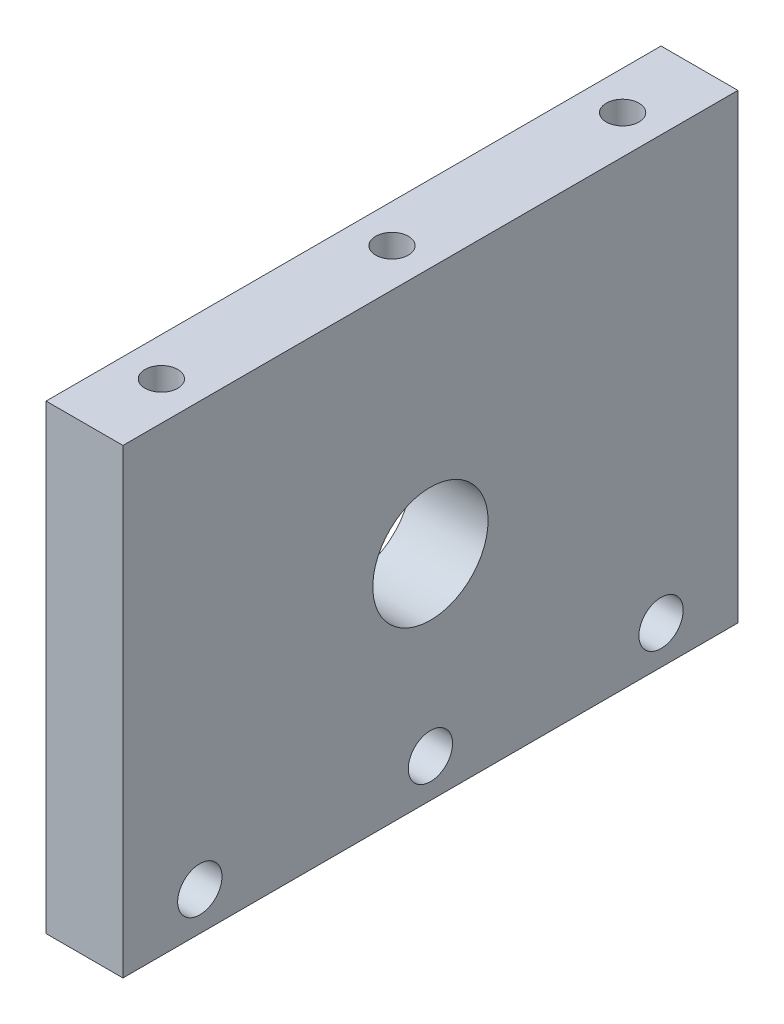
SolidWorks part; units mm, degrees
ref_plane "Front Plane" through (0, 0, 0) normal (0, 0, 1) x (1, 0, 0)
ref_plane "Top Plane" through (0, 0, 0) normal (0, 1, 0) x (1, 0, 0)
ref_plane "Right Plane" through (0, 0, 0) normal (1, 0, 0) x (0, 0, -1)
sketch "Sketch1" plane through (0, 0, 0) normal (1, 0, 0) x (0, 0, -1)
  line L1 (0, 0) -> (-50.8, 0)
  line L2 (0, 0) -> (0, 38.1)
  line L3 (0, 38.1) -> (-50.8, 38.1)
  line L4 (-50.8, 0) -> (-50.8, 38.1)
  dimension "D1" = 38.1
  dimension "D2" = 50.8
extrude "Boss-Extrude1" add sketch "Sketch1" along normal blind 6.35
sketch "Sketch2" plane through (0, 38.1, 0) normal (0, 1, 0) x (1, 0, 0)
  line L0 (0, 0) -> (0, -50.8) construction
  line L1 (6.35, -50.8) -> (0, -50.8) construction
  circle A0 centre (3.175, -44.45) radius 1.7526
  circle A1 centre (3.175, -6.35) radius 1.7526
  circle A3 centre (3.175, -25.4) radius 1.7526
  dimension "D1" = 3.5052
  dimension "D3" = 3.5052
  dimension "D5" = 3.5052
  dimension "D2" = 3.175
  dimension "D4" = 6.35
  dimension "D6" = 25.4
  dimension "D7" = 44.45
sketch "Sketch3" plane through (6.35, 0, 0) normal (1, 0, 0) x (0, 0, -1)
  line L0 (-50.8, 38.1) -> (-50.8, 0) construction
  line L1 (-50.8, 0) -> (0, 0) construction
  circle A0 centre (-44.45, 3.175) radius 1.8288
  circle A1 centre (-25.4, 3.175) radius 1.8288
  circle A2 centre (-6.35, 3.175) radius 1.8288
  dimension "D7" = 3.6576
  dimension "D8" = 3.6576
  dimension "D9" = 3.6576
  dimension "D1" = 6.35
  dimension "D2" = 25.4
  dimension "D3" = 44.45
  dimension "D4" = 3.175
  dimension "D5" = 3.175
  dimension "D6" = 3.175
extrude "Cut-Extrude1" cut sketch "Sketch3" against normal blind 6.35
hole_wizard "#6-32 Tapped Hole1" positions "Sketch10" profile "Sketch11" tap size "#6-32" standard "ANSI Inch"
sketch "Sketch10" plane through (0, 38.1, 0) normal (0, 1, 0) x (1, 0, 0)
  point P0 (3.175, -6.35)
  point P3 (3.175, -25.4)
  point P6 (3.175, -44.45)
sketch "Sketch11" plane through (3.175, 38.1, 6.35) normal (1, 0, 0) x (0, 0, 1)
  line L0 (0, 0) -> (0, 12.7)
  line L1 (0, 12.7) -> (1.3525, 11.8873)
  line L2 (1.3525, 11.8873) -> (1.3525, 0)
  line L5 (1.3525, 0) -> (0, 0)
  line L10 (0, 12.7) -> (-1.3526, 11.8873) construction
  line L11 (0, -6.35) -> (0, 107.95) construction
  dimension "Tap Drill Dia." = 2.7051
  dimension "Tap Drill Depth" = 12.7
  dimension "Drill Angle" = 118
cosmetic thread "Hole Thread1" parameters "D1"=10.16, "D2"=3.5052
cosmetic thread "Hole Thread2" parameters "D1"=10.16, "D2"=3.5052
cosmetic thread "Hole Thread3" parameters "D1"=10.16, "D2"=3.5052
sketch "Sketch12" plane through (6.35, 0, 0) normal (1, 0, 0) x (0, 0, -1)
  line L0 (-50.8, 0) -> (0, 0) construction
  line L1 (-50.8, 38.1) -> (-50.8, 0) construction
  circle A0 centre (-25.4, 17.653) radius 4.7625
  dimension "D1" = 9.525
  dimension "D2" = 17.653
  dimension "D3" = 25.4
extrude "Cut-Extrude3" cut sketch "Sketch12" against normal blind 6.35
